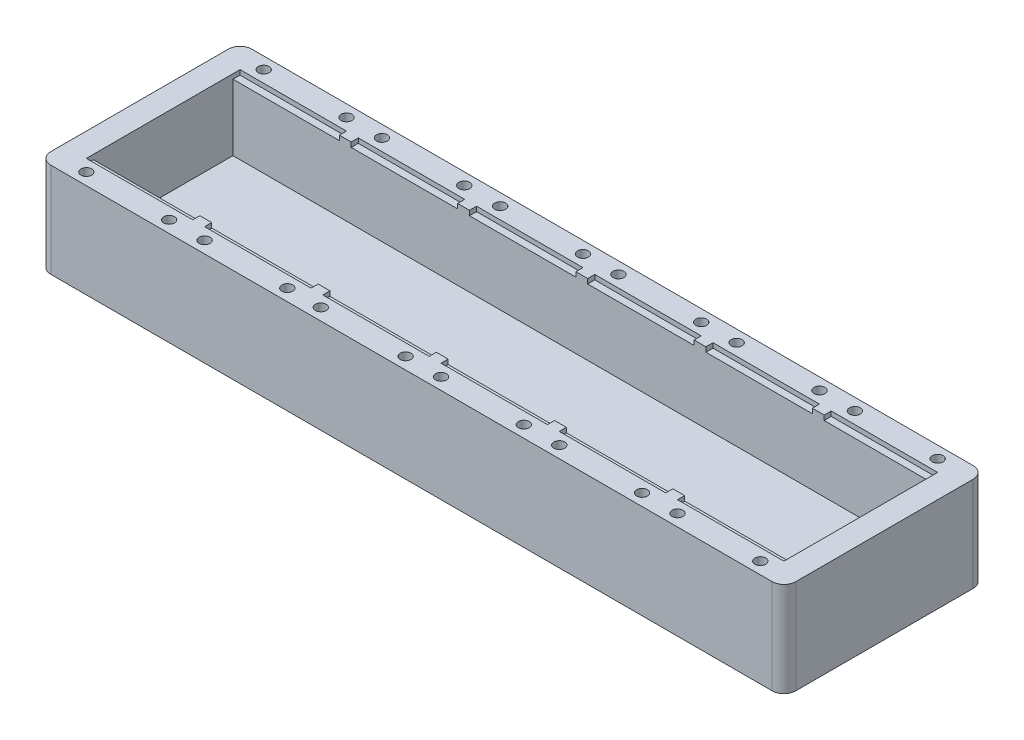
SolidWorks part; units mm, degrees
material "Starkstromplatine"
ref_plane "Ebene vorne" through (0, 0, 0) normal (0, 0, 1) x (1, 0, 0)
ref_plane "Ebene oben" through (0, 0, 0) normal (0, 1, 0) x (1, 0, 0)
ref_plane "Ebene rechts" through (0, 0, 0) normal (1, 0, 0) x (0, 0, -1)
sketch "Skizze2" plane through (0, 0, 0) normal (0, 0, 1) x (1, 0, 0)
  line L1 (0, 0) -> (315, 0)
  line L2 (0, 0) -> (0, 40)
  line L3 (0, 40) -> (315, 40)
  line L4 (315, 0) -> (315, 40)
  dimension "D1" = 315
  dimension "D2" = 40
extrude "Aufsatz-Linear austragen1" add sketch "Skizze2" along normal blind 85
sketch "Skizze4" plane through (0, 40, 0) normal (0, 1, 0) x (1, 0, 0)
  line L1 (10, -13) -> (305, -13)
  line L2 (10, -13) -> (10, -72)
  line L3 (10, -72) -> (305, -72)
  line L4 (305, -13) -> (305, -72)
  line L6 (0, -85) -> (0, 0) construction
  line L7 (315, -85) -> (315, 0) construction
  line L8 (315, -85) -> (0, -85) construction
  dimension "D1" = 59
  dimension "D2" = 13
  dimension "D3" = 10
  dimension "D4" = 10
extrude "Schnitt-Linear austragen1" cut sketch "Skizze4" against normal blind 30
sketch "Skizze11" plane through (0, 40, 0) normal (0, 1, 0) x (1, 0, 0)
  line L0 (10, -72) -> (305, -72) construction
  line L1 (10, -13) -> (55, -13)
  line L2 (10, -13) -> (10, -10)
  line L3 (10, -10) -> (55, -10)
  line L4 (55, -13) -> (55, -10)
  line L5 (55, -72) -> (10, -72)
  line L6 (55, -72) -> (55, -75)
  line L7 (55, -75) -> (10, -75)
  line L8 (10, -72) -> (10, -75)
  line L9 (305, -13) -> (10, -13) construction
  line L10 (60, -75) -> (105, -75)
  line L11 (60, -75) -> (60, -72)
  line L12 (60, -72) -> (105, -72)
  line L13 (105, -75) -> (105, -72)
  line L14 (110, -75.0087) -> (155, -75.0087)
  line L15 (110, -75.0087) -> (110, -72)
  line L16 (110, -72) -> (155, -72)
  line L17 (155, -75.0087) -> (155, -72)
  line L18 (160, -75.0087) -> (205, -75.0087)
  line L19 (160, -75.0087) -> (160, -72)
  line L20 (160, -72) -> (205, -72)
  line L21 (205, -75.0087) -> (205, -72)
  line L22 (210, -75) -> (255, -75)
  line L23 (210, -75) -> (210, -72)
  line L24 (210, -72) -> (255, -72)
  line L25 (255, -75) -> (255, -72)
  line L26 (260, -75) -> (305, -75)
  line L27 (260, -75) -> (260, -72)
  line L28 (260, -72) -> (305, -72)
  line L29 (305, -75) -> (305, -72)
  line L30 (305, -13) -> (260, -13)
  line L31 (305, -13) -> (305, -10)
  line L32 (305, -10) -> (260, -10)
  line L33 (260, -13) -> (260, -10)
  line L35 (255, -13) -> (210, -13)
  line L36 (255, -13) -> (255, -10)
  line L37 (255, -10) -> (210, -10)
  line L38 (210, -13) -> (210, -10)
  line L39 (205, -13) -> (160, -13)
  line L40 (205, -13) -> (205, -10)
  line L41 (205, -10) -> (160, -10)
  line L42 (160, -13) -> (160, -10)
  line L43 (155, -13) -> (110, -13)
  line L44 (155, -13) -> (155, -10)
  line L45 (155, -10) -> (110, -10)
  line L46 (110, -13) -> (110, -10)
  line L47 (105, -13) -> (60, -13)
  line L48 (105, -13) -> (105, -10)
  line L49 (105, -10) -> (60, -10)
  line L50 (60, -13) -> (60, -10)
  dimension "D1" = 45
  dimension "D2" = 3
  dimension "D3" = 45
  dimension "D4" = 5
  dimension "D5" = 5
  dimension "D6" = 5
  dimension "D7" = 5
  dimension "D8" = 5
  dimension "D9" = 5
  dimension "D10" = 45
  dimension "D11" = 45
  dimension "D12" = 45
  dimension "D13" = 45
  dimension "D14" = 45
  dimension "D15" = 5
  dimension "D16" = 5
  dimension "D17" = 5
  dimension "D18" = 5
  dimension "D19" = 45
  dimension "D20" = 45
  dimension "D21" = 45
  dimension "D22" = 45
  dimension "D23" = 3
  dimension "D24" = 3
  dimension "D25" = 3
  dimension "D26" = 3
  dimension "D27" = 3
  dimension "D28" = 3
  dimension "D29" = 3
  dimension "D30" = 3
extrude "Schnitt-Linear austragen4" cut sketch "Skizze11" against normal blind 2
sketch "Skizze17" plane through (0, 40, 0) normal (0, 1, 0) x (1, 0, 0)
  line L0 (55, -75) -> (55, -72) construction
  line L1 (315, 0) -> (0, 0) construction
  line L2 (315, -85) -> (0, -85) construction
  line L3 (10, -72) -> (10, -75) construction
  line L4 (10, -10) -> (10, -75) construction
  line L5 (55, -13) -> (55, -10) construction
  line L6 (60, -72) -> (60, -75) construction
  line L7 (105, -75) -> (105, -72) construction
  line L8 (155, -75.0087) -> (155, -72) construction
  line L10 (160, -72) -> (160, -75.0087) construction
  line L11 (205, -75.0087) -> (205, -72) construction
  line L12 (305, -75) -> (305, -10) construction
  line L13 (260, -72) -> (260, -75) construction
  line L14 (255, -75) -> (255, -72) construction
  line L15 (210, -72) -> (210, -75) construction
  line L16 (60, -10) -> (60, -13) construction
  line L18 (110, -10) -> (110, -13) construction
  circle A0 centre (50, -80) radius 2.3
  circle A1 centre (15, -80) radius 2.3
  circle A2 centre (15, -5) radius 2.3
  circle A3 centre (50, -5) radius 2.3
  circle A4 centre (65, -5) radius 2.3
  circle A5 centre (99.8349, -5) radius 2.3
  circle A6 centre (65, -80) radius 2.3
  circle A7 centre (100, -80) radius 2.3
  circle A8 centre (114.1455, -80) radius 2.3
  circle A9 centre (150, -80) radius 2.3
  circle A10 centre (165, -80) radius 2.3
  circle A11 centre (200, -80) radius 2.3
  circle A12 centre (215, -80) radius 2.3
  circle A13 centre (250, -80) radius 2.3
  circle A14 centre (265, -80) radius 2.3
  circle A15 centre (300, -80) radius 2.3
  circle A16 centre (300, -5) radius 2.3
  circle A17 centre (265, -5) radius 2.3
  circle A18 centre (250, -5) radius 2.3
  circle A19 centre (215, -5) radius 2.3
  circle A20 centre (200, -5) radius 2.3
  circle A21 centre (165, -5) radius 2.3
  circle A22 centre (150, -5) radius 2.3
  circle A23 centre (115, -5) radius 2.3
  dimension "D1" = 4.6
  dimension "D2" = 4.6
  dimension "D3" = 4.6
  dimension "D4" = 4.6
  dimension "D5" = 5
  dimension "D6" = 5
  dimension "D7" = 5
  dimension "D8" = 5
  dimension "D10" = 5
  dimension "D11" = 5
  dimension "D12" = 5
  dimension "D13" = 4.6
  dimension "D14" = 4.6
  dimension "D15" = 4.6
  dimension "D16" = 4.6
  dimension "D17" = 4.6
  dimension "D18" = 4.6
  dimension "D19" = 4.6
  dimension "D20" = 4.6
  dimension "D21" = 4.6
  dimension "D22" = 4.6
  dimension "D23" = 5
  dimension "D25" = 5
  dimension "D26" = 5
  dimension "D27" = 5
  dimension "D28" = 5
  dimension "D29" = 5
  dimension "D30" = 5
  dimension "D31" = 5
  dimension "D32" = 5
  dimension "D33" = 5
  dimension "D34" = 5
  dimension "D35" = 5
  dimension "D36" = 5
  dimension "D37" = 5
  dimension "D38" = 5
  dimension "D39" = 5
  dimension "D40" = 5
  dimension "D41" = 5
  dimension "D42" = 5
  dimension "D43" = 4.6
  dimension "D44" = 4.6
  dimension "D45" = 4.6
  dimension "D46" = 4.6
  dimension "D47" = 4.6
  dimension "D48" = 4.6
  dimension "D49" = 4.6
  dimension "D50" = 4.6
  dimension "D51" = 4.6
  dimension "D52" = 4.6
  dimension "D53" = 5
  dimension "D54" = 5
  dimension "D55" = 5
  dimension "D9" = 5
  dimension "D24" = 5
extrude "Schnitt-Linear austragen6" cut sketch "Skizze17" against normal blind 4
fillet "Verrundung2" radius 5 1 edges at (0, 20, 85)
fillet "Verrundung3" radius 5 1 edges at (0, 20, 0)
fillet "Verrundung4" radius 5 1 edges at (315, 20, 0)
fillet "Verrundung6" radius 5 1 edges at (315, 20, 85)
